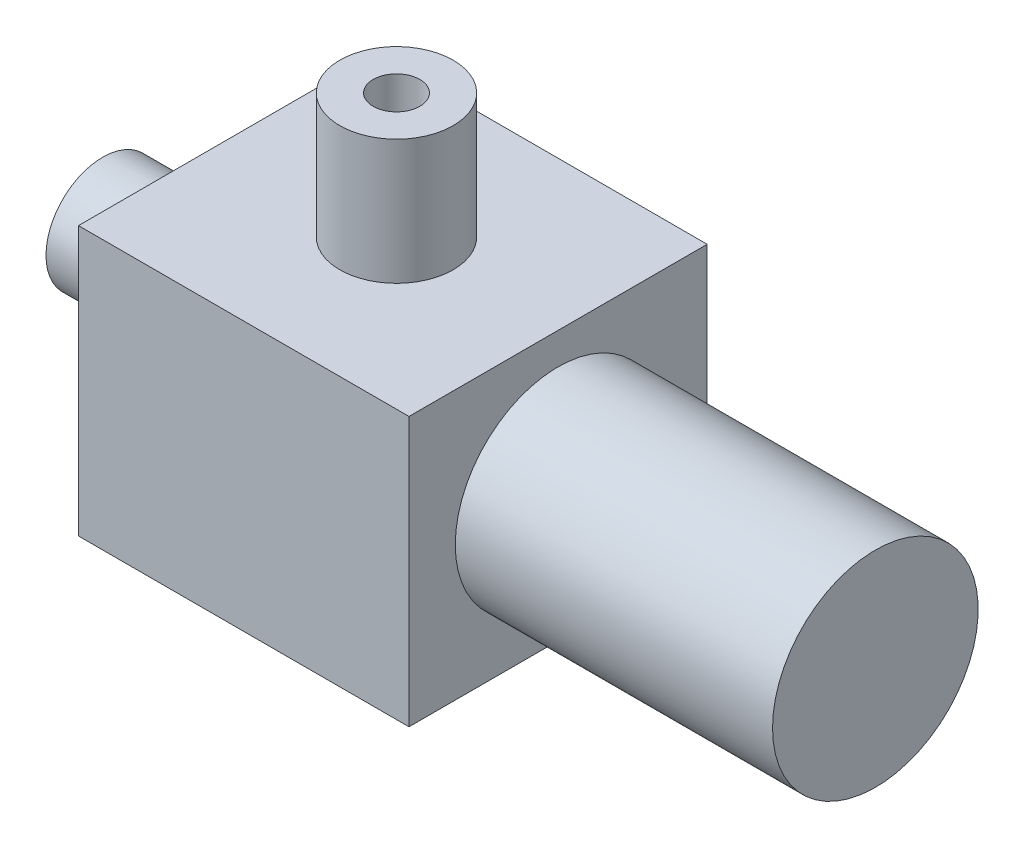
SolidWorks part; units mm, degrees
ref_plane "Front Plane" through (0, 0, 0) normal (0, 0, 1) x (1, 0, 0)
ref_plane "Top Plane" through (0, 0, 0) normal (0, 1, 0) x (1, 0, 0)
ref_plane "Right Plane" through (0, 0, 0) normal (1, 0, 0) x (0, 0, -1)
sketch "Body Sketch" plane through (0, 0, 0) normal (0, 0, 1) x (1, 0, 0)
  line L0 (17, -18.3) -> (62, -18.3)
  line L1 (62, -18.3) -> (62, 18.3)
  line L2 (62, 18.3) -> (17, 18.3)
  line L3 (17, 18.3) -> (17, -18.3)
extrude "Body" add sketch "Body Sketch" along normal mid plane 40.6
ref_axis "Engine Axis" through (110.46, 0, 0) along (-1, 0, 0)
sketch "Inlet Sketch" plane through (0, 0, 0) normal (0, 0, 1) x (1, 0, 0)
  line L0 (-1000, 0) -> (1000, 0) construction
  line L1 (0, 0) -> (17, 0)
  line L2 (17, 0) -> (17, 7.722)
  line L3 (17, 7.722) -> (0, 7.722)
  line L4 (0, 7.722) -> (0, 0)
revolve "Inlet" add sketch "Inlet Sketch" angle 360 about L0
sketch "Spring Cap Sketch" plane through (0, 0, 0) normal (0, 0, 1) x (1, 0, 0)
  line L0 (-1000, 0) -> (1000, 0) construction
  line L1 (62, 0) -> (105.2, 0)
  line L2 (105.2, 0) -> (105.2, 14)
  line L3 (105.2, 14) -> (62, 14)
  line L4 (62, 14) -> (62, 0)
revolve "Spring Cap" add sketch "Spring Cap Sketch" angle 360 about L0
sketch "Outlet Sketch" plane through (0, 0, 0) normal (0, 0, 1) x (1, 0, 0)
  line L0 (40, 0) -> (40, 200) construction
  line L1 (40, 18.3) -> (47.722, 18.3)
  line L2 (47.722, 18.3) -> (47.722, 35.3)
  line L3 (47.722, 35.3) -> (40, 35.3)
  line L4 (40, 35.3) -> (40, 18.3)
revolve "Outlet" add sketch "Outlet Sketch" angle 360 about L0
sketch "Inlet Socket Sketch" plane through (0, 0, 0) normal (0, 0, 1) x (1, 0, 0)
  line L0 (-1000, 0) -> (1000, 0) construction
  line L1 (-1, 0) -> (15.2, 0)
  line L2 (15.2, 0) -> (15.2, 3.175)
  line L3 (15.2, 3.175) -> (-1, 3.175)
  line L4 (-1, 3.175) -> (-1, 0)
revolve "Inlet Socket" cut sketch "Inlet Socket Sketch" angle 360 about L0
sketch "Outlet Socket Sketch" plane through (0, 0, 0) normal (0, 0, 1) x (1, 0, 0)
  line L0 (40, 0) -> (40, 200) construction
  line L1 (40, 20.1) -> (43.175, 20.1)
  line L2 (43.175, 20.1) -> (43.175, 36.3)
  line L3 (43.175, 36.3) -> (40, 36.3)
  line L4 (40, 36.3) -> (40, 20.1)
revolve "Outlet Socket" cut sketch "Outlet Socket Sketch" angle 360 about L0
